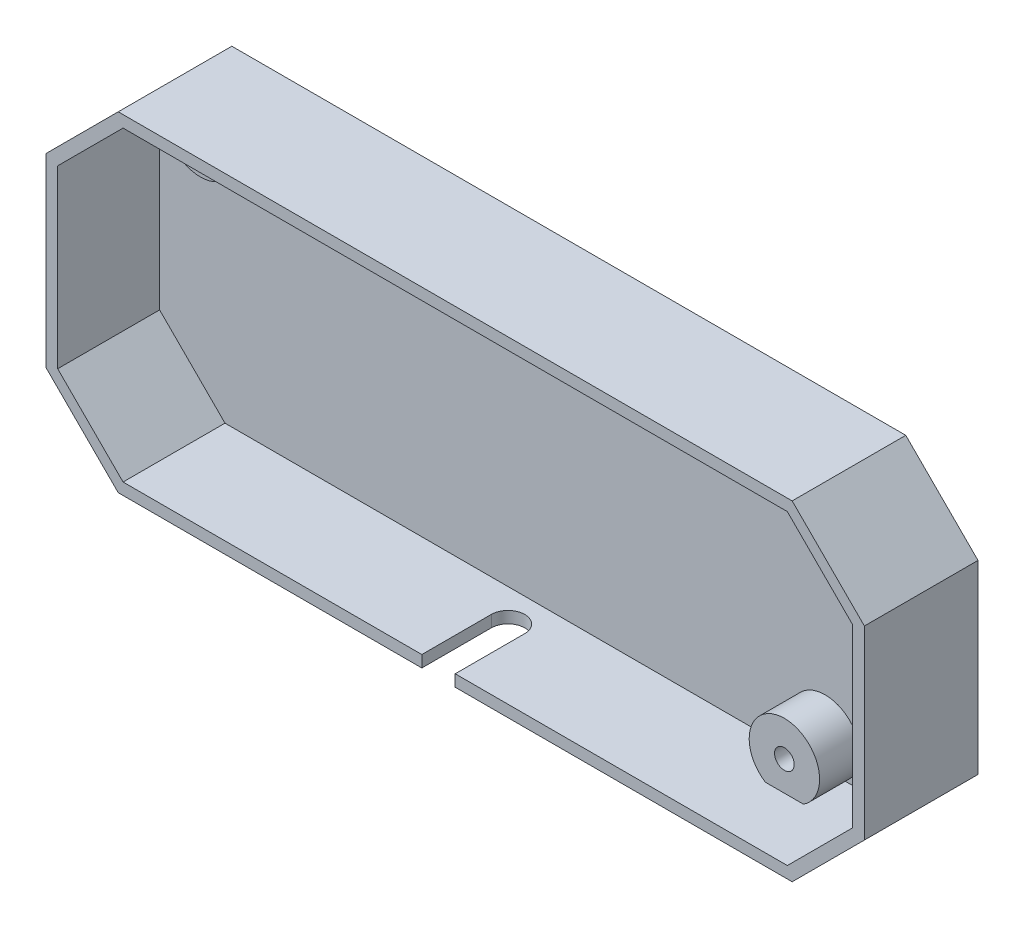
SolidWorks part; units mm, degrees
ref_plane "Front Plane" through (0, 0, 0) normal (0, 0, 1) x (1, 0, 0)
ref_plane "Top Plane" through (0, 0, 0) normal (0, 1, 0) x (1, 0, 0)
ref_plane "Right Plane" through (0, 0, 0) normal (1, 0, 0) x (0, 0, -1)
sketch "Sketch1" plane through (0, 0, 0) normal (0, 0, 1) x (1, 0, 0)
  line L1 (-28.0415, -11.3029) -> (28.0415, -11.3029)
  line L2 (-28.0415, -11.3029) -> (-28.0415, 11.3029)
  line L3 (-28.0415, 11.3029) -> (28.0415, 11.3029)
  line L4 (28.0415, -11.3029) -> (28.0415, 11.3029)
  line L5 (-28.0415, -11.3029) -> (28.0415, 11.3029) construction
  line L6 (-28.0415, 11.3029) -> (28.0415, -11.3029) construction
  point P0 (0, 0)
  dimension "D1" = 56.083
  dimension "D2" = 22.6058
extrude "Boss-Extrude1" add sketch "Sketch1" along normal blind 0.8
sketch "Sketch2" plane through (0, 0, 0.8) normal (0, 0, 1) x (1, 0, 0)
  line L0 (-28.0415, -6.3532) -> (-23.0918, -11.3029)
  line L1 (-28.0415, 11.3029) -> (-28.0415, -11.3029) construction
  line L2 (-28.0415, 6.3532) -> (-23.0918, 11.3029)
  line L3 (28.0415, 11.3029) -> (-28.0415, 11.3029) construction
  line L4 (-23.0918, 11.3029) -> (-28.0415, 11.3029)
  line L5 (-28.0415, 11.3029) -> (-28.0415, 6.3532)
  line L6 (-28.0415, -11.3029) -> (28.0415, -11.3029) construction
  line L7 (-23.0918, -11.3029) -> (-28.0415, -11.3029)
  line L8 (-28.0415, -11.3029) -> (-28.0415, -6.3532)
  line L9 (23.0918, -11.3029) -> (28.0415, -6.3532)
  line L10 (28.0415, -11.3029) -> (28.0415, 11.3029) construction
  line L11 (28.0415, -6.3532) -> (28.0415, -11.3029)
  line L12 (28.0415, -11.3029) -> (23.0918, -11.3029)
  line L13 (23.0918, 11.3029) -> (28.0415, 6.3532)
  line L14 (28.0415, 6.3532) -> (28.0415, 11.3029)
  line L15 (28.0415, 11.3029) -> (23.0918, 11.3029)
  dimension "D1" = 7
  dimension "D2" = 7
  dimension "D3" = 7
  dimension "D4" = 7
  dimension "D5" = 45
  dimension "D6" = 45
  dimension "D7" = 45
  dimension "D8" = 45
extrude "Cut-Extrude1" cut sketch "Sketch2" against normal through all
sketch "Sketch3" plane through (0, 0, 0.8) normal (0, 0, 1) x (1, 0, 0)
  line L0 (23.0918, 11.3029) -> (-23.0918, 11.3029)
  line L1 (-23.0918, 11.3029) -> (-28.0415, 6.3532)
  line L2 (-28.0415, 6.3532) -> (-28.0415, -6.3532)
  line L3 (-28.0415, -6.3532) -> (-23.0918, -11.3029)
  line L4 (-23.0918, -11.3029) -> (23.0918, -11.3029)
  line L5 (23.0918, -11.3029) -> (28.0415, -6.3532)
  line L6 (28.0415, -6.3532) -> (28.0415, 6.3532)
  line L7 (28.0415, 6.3532) -> (23.0918, 11.3029)
  line L48 (-22.7604, 10.5029) -> (-27.2415, 6.0218)
  line L49 (-27.2415, 6.0218) -> (-27.2415, -6.0218)
  line L50 (-27.2415, -6.0218) -> (-22.7604, -10.5029)
  line L51 (-22.7604, -10.5029) -> (22.7604, -10.5029)
  line L52 (22.7604, -10.5029) -> (27.2415, -6.0218)
  line L53 (27.2415, -6.0218) -> (27.2415, 6.0218)
  line L54 (27.2415, 6.0218) -> (22.7604, 10.5029)
  line L55 (22.7604, 10.5029) -> (-22.7604, 10.5029)
  line L56 (-22.7604, 10.5029) -> (-27.2415, 6.0218)
  line L57 (-27.2415, 6.0218) -> (-27.2415, -6.0218)
  line L58 (-27.2415, -6.0218) -> (-22.7604, -10.5029)
  line L59 (-22.7604, -10.5029) -> (22.7604, -10.5029)
  line L60 (22.7604, -10.5029) -> (27.2415, -6.0218)
  line L61 (27.2415, -6.0218) -> (27.2415, 6.0218)
  line L62 (27.2415, 6.0218) -> (22.7604, 10.5029)
  line L63 (22.7604, 10.5029) -> (-22.7604, 10.5029)
  dimension "D1" = 0.8
  dimension "D2" = 0.8
extrude "Boss-Extrude2" add sketch "Sketch3" along normal blind 6.985
sketch "Sketch4" plane through (0, 0, 0.8) normal (0, 0, 1) x (1, 0, 0)
  line L0 (22.7604, 10.5029) -> (-22.7604, 10.5029) construction
  line L1 (-22.7604, -10.5029) -> (22.7604, -10.5029) construction
  line L2 (-27.2415, 6.0218) -> (-27.2415, -6.0218) construction
  circle A0 centre (-21.6535, 8.4709) radius 2.413
  circle A1 centre (18.3677, -8.4709) radius 2.413
  dimension "D1" = 4.826
  dimension "D2" = 4.826
  dimension "D3" = 2.032
  dimension "D4" = 2.032
  dimension "D5" = 43.4594
  dimension "D6" = 5.588
extrude "Boss-Extrude3" add sketch "Sketch4" along normal blind 2.794
sketch "Sketch5" plane through (0, 0, 3.594) normal (0, 0, 1) x (1, 0, 0)
  circle A0 centre (-21.6535, 8.4709) radius 0.6731
  circle A1 centre (18.3677, -8.4709) radius 0.6731
  dimension "D1" = 1.3462
  dimension "D2" = 1.3462
extrude "Cut-Extrude2" cut sketch "Sketch5" against normal up to surface (2.794 mm away) up to face at (1.4959, -0.9958, 0.8)
sketch "Sketch6" plane through (0, -11.3029, 0) normal (0, -1, 0) x (-1, 0, 0)
  line L0 (2.286, -7.785) -> (2.286, -3.0225)
  line L1 (23.0918, -7.785) -> (-23.0918, -7.785) construction
  line L2 (0, -7.785) -> (2.286, -7.785)
  line L3 (0, -3.0225) -> (0, -7.785)
  arc A0 (2.286, -3.0225) -> (0, -3.0225) centre (1.143, -3.0225) ccw
  dimension "D2" = 1.143
  dimension "D1" = 2.286
  dimension "D3" = 4.7625
extrude "Cut-Extrude3" cut sketch "Sketch6" against normal blind 2.794
